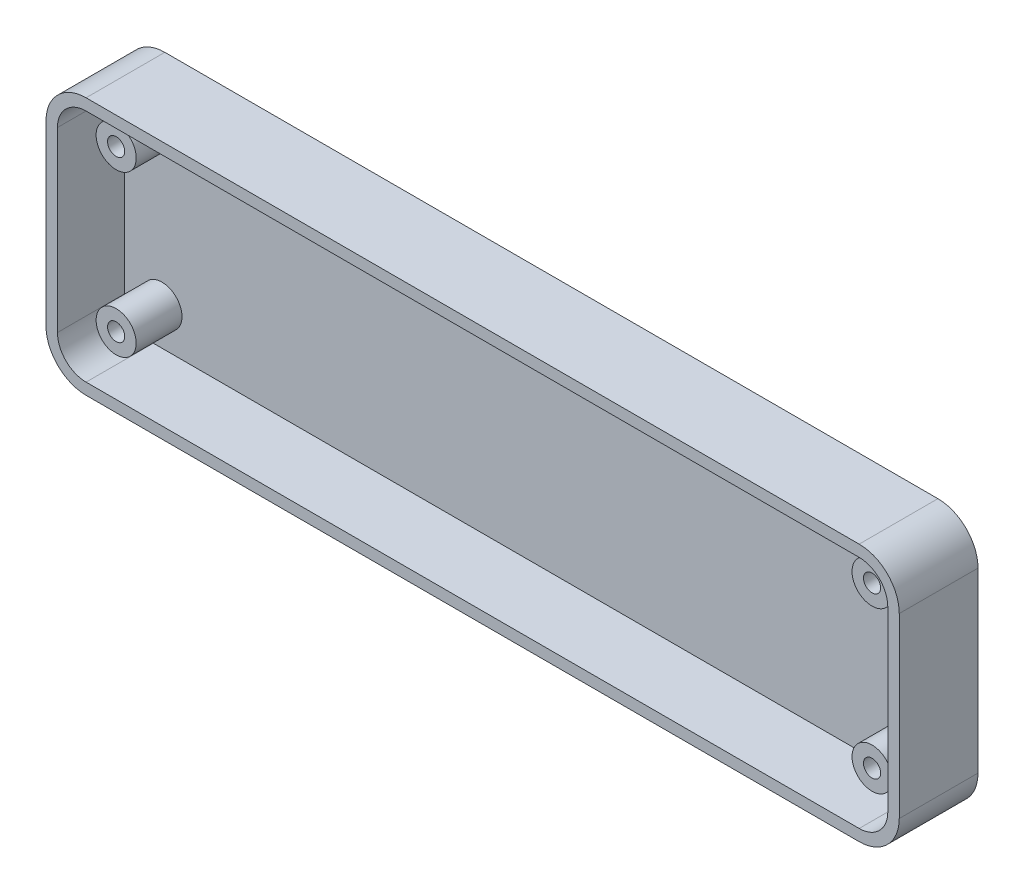
SolidWorks part; units mm, degrees
ref_plane "Alzado" through (0, 0, 0) normal (0, 0, 1) x (1, 0, 0)
ref_plane "Planta" through (0, 0, 0) normal (0, 1, 0) x (1, 0, 0)
ref_plane "Vista lateral" through (0, 0, 0) normal (1, 0, 0) x (0, 0, -1)
sketch "Croquis1" plane through (0, 0, 0) normal (0, 0, 1) x (1, 0, 0)
  line L0 (-67.5, 22.5) -> (67.5, 22.5)
  line L1 (-70, -18) -> (70, -18) construction
  line L2 (-70, -18) -> (-70, 18) construction
  line L3 (-70, 18) -> (70, 18) construction
  line L4 (70, -18) -> (70, 18) construction
  line L5 (-70, -18) -> (70, 18) construction
  line L6 (-70, 18) -> (70, -18) construction
  line L7 (-67.5, 20.5) -> (67.5, 20.5)
  line L8 (-72.5, 15.5) -> (-72.5, -15.5)
  line L9 (-67.5, -20.5) -> (67.5, -20.5)
  line L10 (72.5, 15.5) -> (72.5, -15.5)
  line L11 (-72.5, 20.5) -> (72.5, -20.5) construction
  line L12 (-72.5, -20.5) -> (72.5, 20.5) construction
  line L13 (74.5, 15.5) -> (74.5, -15.5)
  line L14 (-67.5, -22.5) -> (67.5, -22.5)
  line L15 (-74.5, 15.5) -> (-74.5, -15.5)
  arc A0 (67.5, 20.5) -> (72.5, 15.5) centre (67.5, 15.5) cw
  arc A1 (67.5, -20.5) -> (72.5, -15.5) centre (67.5, -15.5) ccw
  arc A2 (-67.5, -20.5) -> (-72.5, -15.5) centre (-67.5, -15.5) cw
  arc A3 (-72.5, 15.5) -> (-67.5, 20.5) centre (-67.5, 15.5) cw
  arc A4 (67.5, 22.5) -> (74.5, 15.5) centre (67.5, 15.5) cw
  arc A5 (67.5, -22.5) -> (74.5, -15.5) centre (67.5, -15.5) ccw
  arc A6 (-67.5, -22.5) -> (-74.5, -15.5) centre (-67.5, -15.5) cw
  arc A7 (-74.5, 15.5) -> (-67.5, 22.5) centre (-67.5, 15.5) cw
  circle A8 centre (66, 14) radius 1.5
  circle A9 centre (66, -14) radius 1.5
  circle A10 centre (-66, 14) radius 1.5
  circle A11 centre (-66, -14) radius 1.5
  circle A12 centre (-66, 14) radius 3.5
  circle A13 centre (66, 14) radius 3.5
  circle A14 centre (66, -14) radius 3.5
  circle A15 centre (-66, -14) radius 3.5
  point P0 (0, 0)
  point P6 (0, 0)
  dimension "D5" = 5
  dimension "D7" = 3
  dimension "D8" = 4
  dimension "D9" = 4
  dimension "D11" = 4
  dimension "D12" = 2
  dimension "D1" = 140
  dimension "D2" = 36
  dimension "D3" = 145
  dimension "D4" = 41
  dimension "D10" = 4
  dimension "D6" = 2
  dimension "D13" = 2
  dimension "D14" = 2
  dimension "D15" = 2
extrude "Saliente-Extruir1" add sketch "Croquis1" against normal blind 13.75 contours A7 L15 A6 L14 A5 L13 A4 L0 L8 A3 L7 A0 L10 A1 L9 A2 | A13 A8 | A14 A9 | A12 A10 | A15 A11 region at (0, 20.9435, 0) region at (-69.401, 14, 0) region at (62.599, 14, 0) region at (62.599, -14, 0) region at (-69.401, -14, 0)
sketch "Croquis3" plane through (0, 0, -13.75) normal (0, 0, -1) x (-1, 0, 0)
  line L0 (72.5, 15.5) -> (72.5, -15.5) construction
  line L1 (67.5, -20.5) -> (-67.5, -20.5) construction
  line L2 (-72.5, 15.5) -> (-72.5, -15.5) construction
  line L3 (67.5, 20.5) -> (-67.5, 20.5) construction
  line L4 (72.5, 15.5) -> (72.5, -15.5)
  line L5 (67.5, -20.5) -> (-67.5, -20.5)
  line L6 (-72.5, 15.5) -> (-72.5, -15.5)
  line L7 (67.5, 20.5) -> (-67.5, 20.5)
  arc A0 (67.5, -20.5) -> (72.5, -15.5) centre (67.5, -15.5) ccw construction
  arc A1 (72.5, 15.5) -> (67.5, 20.5) centre (67.5, 15.5) ccw construction
  arc A2 (-72.5, -15.5) -> (-67.5, -20.5) centre (-67.5, -15.5) ccw construction
  arc A3 (-67.5, 20.5) -> (-72.5, 15.5) centre (-67.5, 15.5) ccw construction
  arc A4 (67.5, -20.5) -> (72.5, -15.5) centre (67.5, -15.5) ccw
  arc A5 (72.5, 15.5) -> (67.5, 20.5) centre (67.5, 15.5) ccw
  arc A6 (-72.5, -15.5) -> (-67.5, -20.5) centre (-67.5, -15.5) ccw
  arc A7 (-67.5, 20.5) -> (-72.5, 15.5) centre (-67.5, 15.5) ccw
extrude "Saliente-Extruir2" add sketch "Croquis3" against normal blind 2
sketch "Croquis5" plane through (0, 0, 0) normal (0, 0, 1) x (1, 0, 0)
  circle A0 centre (66, -14) radius 1.5 construction
  circle A1 centre (66, -14) radius 3.5 construction
  circle A2 centre (66, 14) radius 1.5 construction
  circle A3 centre (66, 14) radius 3.5 construction
  circle A4 centre (-66, -14) radius 1.5 construction
  circle A5 centre (-66, -14) radius 3.5 construction
  circle A6 centre (-66, 14) radius 1.5 construction
  circle A7 centre (-66, 14) radius 3.5 construction
  circle A8 centre (66, -14) radius 1.5
  circle A9 centre (66, -14) radius 3.5
  circle A10 centre (66, 14) radius 1.5
  circle A11 centre (66, 14) radius 3.5
  circle A12 centre (-66, -14) radius 1.5
  circle A13 centre (-66, -14) radius 3.5
  circle A14 centre (-66, 14) radius 1.5
  circle A15 centre (-66, 14) radius 3.5
extrude "Cortar-Extruir1" cut sketch "Croquis5" against normal blind 3.75
